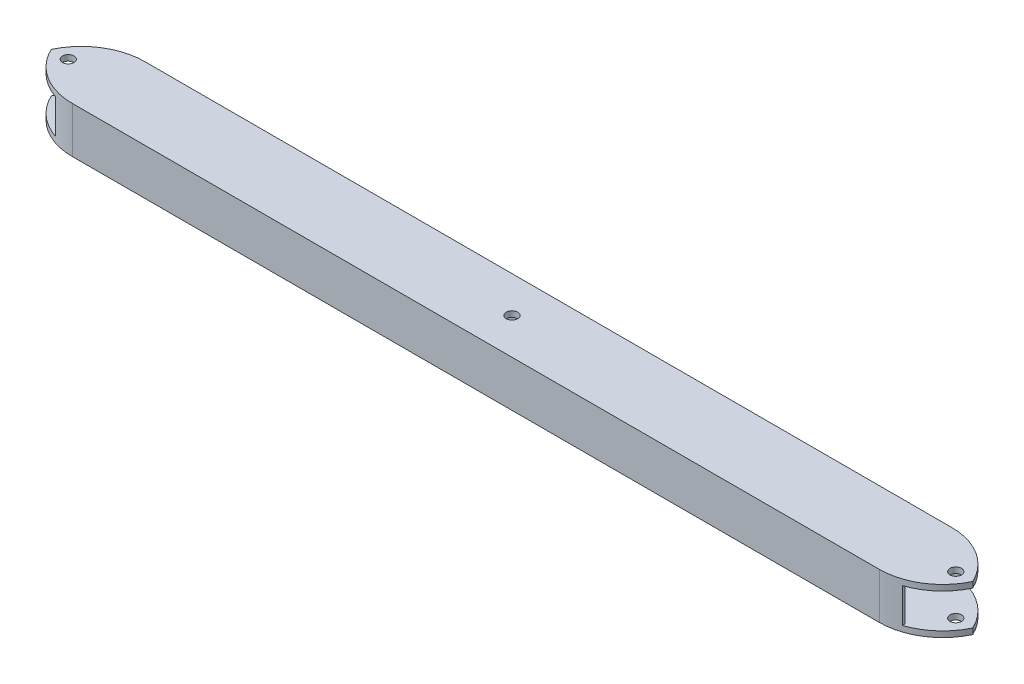
SolidWorks part; units mm, degrees
ref_plane "Front Plane" through (0, 0, 0) normal (0, 0, 1) x (1, 0, 0)
ref_plane "Top Plane" through (0, 0, 0) normal (0, 1, 0) x (1, 0, 0)
ref_plane "Right Plane" through (0, 0, 0) normal (1, 0, 0) x (0, 0, -1)
sketch "Sketch1" plane through (0, 0, 0) normal (0, 1, 0) x (1, 0, 0)
  line L0 (0, 0) -> (515.5, 0)
  line L1 (515.5, 0) -> (515.5, -40)
  line L2 (515.5, -40) -> (0, -40)
  line L3 (0, -40) -> (0, 0)
  line L4 (257.75, 0) -> (257.75, -40) construction
  line L5 (0, -20) -> (515.5, -20) construction
  circle A3 centre (257.75, -20) radius 3.175
  circle A6 centre (12.78, -20) radius 3.175
  circle A8 centre (502.72, -20) radius 3.175
  circle A9 centre (12.78, -20) radius 3.175 construction
  dimension "D3" = 6.35
  dimension "D5" = 244.97
  dimension "D4" = 6.35
  dimension "D1" = 515.5
  dimension "D2" = 40
extrude "Boss-Extrude1" add sketch "Sketch1" along normal blind 25.4
sketch "Sketch2" plane through (0, 0, 0) normal (-1, 0, 0) x (0, 0, 1)
  line L14 (3.175, 22.225) -> (3.175, 3.175)
  line L15 (3.175, 3.175) -> (36.825, 3.175)
  line L16 (36.825, 3.175) -> (36.825, 22.225)
  line L17 (36.825, 22.225) -> (3.175, 22.225)
  line L18 (3.175, 22.225) -> (3.175, 3.175)
  line L19 (3.175, 3.175) -> (36.825, 3.175)
  line L20 (36.825, 3.175) -> (36.825, 22.225)
  line L21 (36.825, 22.225) -> (3.175, 22.225)
  dimension "D1" = 3.175
extrude "Cut-Extrude1" cut sketch "Sketch2" against normal up to surface (515.5 mm away) up to face at (515.5, 12.7, 20)
sketch "Sketch4" plane through (0, 0, 0) normal (-1, 0, 0) x (0, 0, 1)
  line L1 (40, 25.4) -> (40, 0) construction
  line L2 (40, 22.225) -> (40, 3.175)
  line L3 (40, 3.175) -> (0, 3.175)
  line L4 (0, 25.4) -> (0, 0) construction
  line L5 (0, 3.175) -> (0, 22.225)
  line L7 (0, 22.225) -> (40, 22.225)
  line L8 (0, 25.4) -> (40, 25.4) construction
  line L9 (3.175, 3.175) -> (36.825, 3.175) construction
  dimension "D2" = 3.175
extrude "Cut-Extrude2" cut sketch "Sketch4" against normal blind 24
ref_plane "Plane1" through (257.75, 0, 0) normal (-1, 0, 0) x (0, 0, 1)
mirror "Mirror1" about plane through (257.75, 0, 0) normal (-1, 0, 0) of "Cut-Extrude2"
fillet "Fillet1" radius 35 8 edges at (515.5, 1.5875, 0) (515.5, 23.8125, 0) (515.5, 1.5875, 40) (515.5, 23.8125, 40) (0, 1.5875, 40) (0, 23.8125, 40) (0, 1.5875, 0) (0, 23.8125, 0)
sketch "Sketch5" plane through (0, 25.4, 0) normal (0, 1, 0) x (1, 0, 0)
  circle A0 centre (12.78, -20) radius 3.175 construction
  circle A1 centre (502.72, -20) radius 3.175 construction
